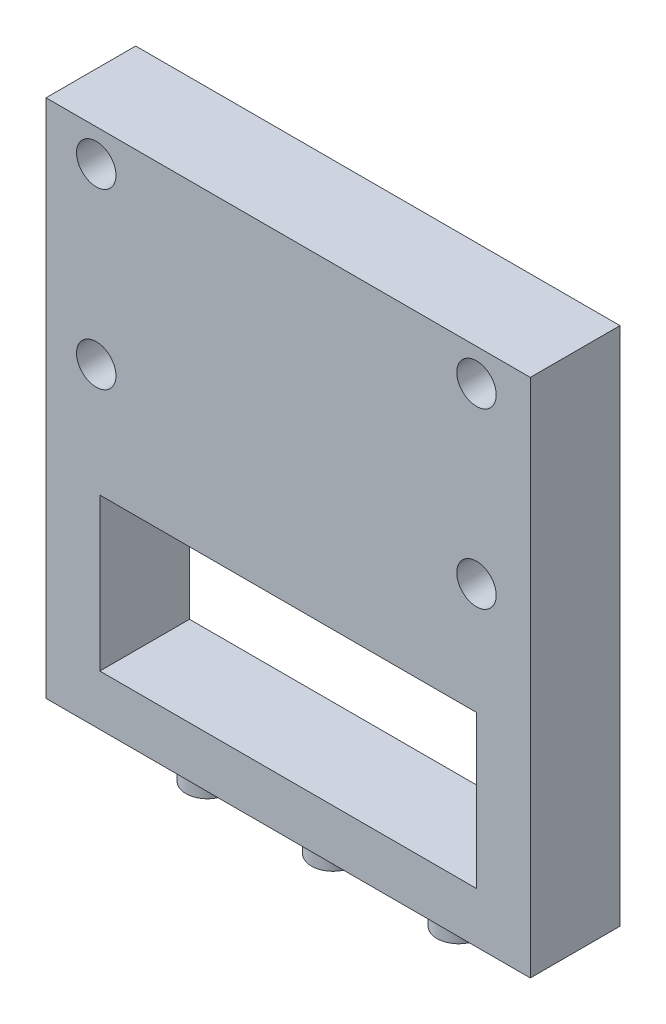
SolidWorks part; units mm, degrees
ref_plane "Front Plane" through (0, 0, 0) normal (0, 0, 1) x (1, 0, 0)
ref_plane "Top Plane" through (0, 0, 0) normal (0, 1, 0) x (1, 0, 0)
ref_plane "Right Plane" through (0, 0, 0) normal (1, 0, 0) x (0, 0, -1)
sketch "Sketch1" plane through (0, 0, 0) normal (0, 0, 1) x (1, 0, 0)
  line L1 (-13.5, 14.5) -> (13.5, 14.5)
  line L2 (-13.5, 14.5) -> (-13.5, -14.5)
  line L3 (-13.5, -14.5) -> (13.5, -14.5)
  line L4 (13.5, 14.5) -> (13.5, -14.5)
  line L5 (-13.5, 14.5) -> (13.5, -14.5) construction
  line L6 (-13.5, -14.5) -> (13.5, 14.5) construction
  point P0 (0, 0)
  dimension "D1" = 27
  dimension "D2" = 29
extrude "Boss-Extrude1" add sketch "Sketch1" along normal blind 5
sketch "Sketch2" plane through (0, -14.5, 0) normal (0, -1, 0) x (1, 0, 0)
  line L0 (-13.5, 2.5) -> (13.5, 2.5) construction
  line L1 (-13.5, 5) -> (-13.5, 0) construction
  line L2 (13.5, 5) -> (13.5, 0) construction
  circle A0 centre (-7, 2.5) radius 1.2
  circle A1 centre (0, 2.5) radius 1.2
  circle A2 centre (7, 2.5) radius 1.2
  point P13 (13.5, 2.5)
  dimension "D1" = 2.4
  dimension "D2" = 7
  dimension "D3" = 7
sketch "Sketch3" plane through (0, 0, 5) normal (0, 0, 1) x (1, 0, 0)
  line L0 (0, 14.5) -> (0, -14.5) construction
  line L1 (13.5, 14.5) -> (-13.5, 14.5) construction
  line L2 (-13.5, -14.5) -> (13.5, -14.5) construction
  line L3 (-13.5, 0) -> (13.5, 0) construction
  line L4 (-13.5, 14.5) -> (-13.5, -14.5) construction
  line L5 (13.5, -14.5) -> (13.5, 14.5) construction
  line L6 (-12.5, 15.7476) -> (12.5, 15.7476) construction
  line L7 (-13.5, -9.36) -> (13.5, -9.36) construction
  line L8 (-5.4, 5.4) -> (5.4, 5.4) construction
  line L9 (-5.4, 5.4) -> (-5.4, -5.4) construction
  line L10 (-5.4, -5.4) -> (5.4, -5.4) construction
  line L11 (5.4, 5.4) -> (5.4, -5.4) construction
  line L12 (-5.4, 5.4) -> (5.4, -5.4) construction
  line L13 (-5.4, -5.4) -> (5.4, 5.4) construction
  line L14 (-10.7, 5.4) -> (-10.7, 0.65) construction
  circle A0 centre (-10.7, 12.7) radius 1.1
  circle A1 centre (10.5, 12.7) radius 1.1
  circle A2 centre (-10.7, 12.7) radius 2.375 construction
  circle A3 centre (-10.7, 3.025) radius 2.375 construction
  circle A4 centre (-10.7, 3.025) radius 1.1
  circle A5 centre (10.5, 3.025) radius 1.1
  circle A6 centre (0, 0) radius 3.475 construction
  point P22 (0, 15.7476)
  point P24 (0, 0)
  dimension "D1" = 2.2
  dimension "D5" = 4.75
  dimension "D6" = 4.75
  dimension "D8" = 2.2
  dimension "D13" = 6.95
  dimension "D7" = 7.3
  dimension "D2" = 1.8
  dimension "D3" = 1.8
  dimension "D4" = 2
  dimension "D9" = 10.8
  dimension "D10" = 25
  dimension "D11" = 10.8
  dimension "D12" = 7.3
  dimension "D14" = 23.86
  dimension "D15" = 14.5
  dimension "D16" = 21.2
  dimension "D17" = 9.675
  dimension "D18" = 9.36
  dimension "D19" = 14.5
extrude "Cut-Extrude2" cut sketch "Sketch3" against normal blind 10
sketch "Sketch4" plane through (0, 0, 5) normal (0, 0, 1) x (1, 0, 0)
  line L0 (0, 14.5) -> (0, -14.5) construction
  line L1 (13.5, 14.5) -> (-13.5, 14.5) construction
  line L2 (-13.5, -14.5) -> (13.5, -14.5) construction
  line L4 (-10.5, -3.1791) -> (10.5, -3.1791)
  line L5 (-10.5, -3.1791) -> (-10.5, -11.6791)
  line L6 (-10.5, -11.6791) -> (10.5, -11.6791)
  line L7 (10.5, -3.1791) -> (10.5, -11.6791)
  line L8 (-10.5, -3.1791) -> (10.5, -11.6791) construction
  line L9 (-10.5, -11.6791) -> (10.5, -3.1791) construction
  point P6 (0, -7.4291)
  dimension "D1" = 21
  dimension "D2" = 8.5
extrude "Cut-Extrude3" cut sketch "Sketch4" against normal blind 10
extrude "Boss-Extrude2" add sketch "Sketch2" along normal blind 2
